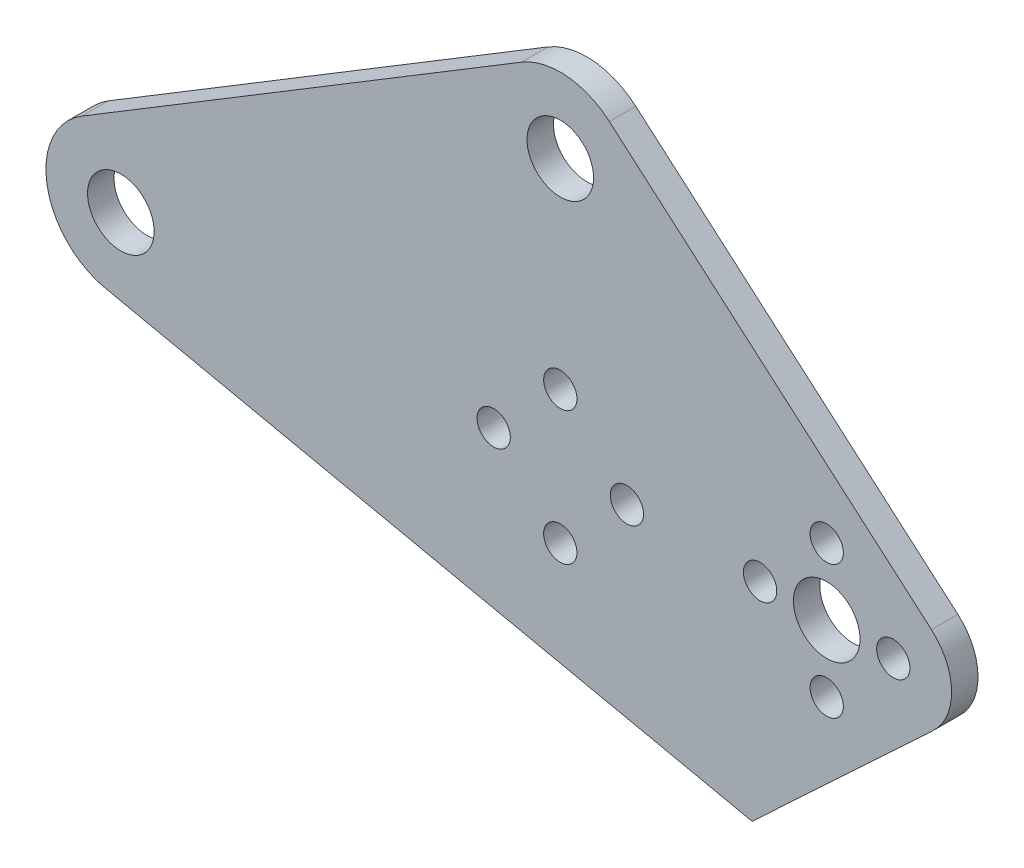
SolidWorks part; units mm, degrees
ref_plane "Front Plane" through (0, 0, 0) normal (0, 0, 1) x (1, 0, 0)
ref_plane "Top Plane" through (0, 0, 0) normal (0, 1, 0) x (1, 0, 0)
ref_plane "Right Plane" through (0, 0, 0) normal (1, 0, 0) x (0, 0, -1)
sketch "Sketch1" plane through (0, 0, 0) normal (0, 0, 1) x (1, 0, 0)
  line L0 (0, 18.4752) -> (52.7846, -12) construction
  line L1 (0, 0) -> (44.7846, 0) construction
  line L2 (-4.6657, 7.6962) -> (48.1189, 39.6962)
  line L3 (58.677, 38.8029) -> (97.3676, 5.2912)
  line L4 (97.5633, -5.1151) -> (75.825, -25.4239)
  line L5 (-1.8827, -8.8009) -> (75.825, -25.4239)
  circle A0 centre (0, 0) radius 4
  circle A1 centre (84.7846, 0) radius 4
  circle A3 centre (60.7846, 0) radius 2
  circle A5 centre (52.7846, -8) radius 2
  circle A6 centre (44.7846, 0) radius 2
  circle A7 centre (52.7846, 8) radius 2
  circle A8 centre (52.7846, 32) radius 4
  circle A9 centre (92.7846, 0) radius 2
  circle A10 centre (84.7846, -8) radius 2
  circle A11 centre (76.7846, 0) radius 2
  circle A12 centre (84.7846, 8) radius 2
  arc A13 (-4.6657, 7.6962) -> (-1.8827, -8.8009) centre (0, 0) ccw
  arc A14 (48.1189, 39.6962) -> (58.677, 38.8029) centre (52.7846, 32) cw
  arc A15 (97.3676, 5.2912) -> (97.5633, -5.1151) centre (92.7846, 0) cw
  point P10 (52.7846, 0)
  point P15 (52.7846, 0)
  point P31 (84.7846, 0)
  point P35 (98.4241, 3.0009)
  point P36 (0, 0)
  point P38 (0, 0)
  point P39 (0, 0)
  point P40 (0, 0)
  point P41 (0, 0)
  dimension "D1" = 8
  dimension "D3" = 4
  dimension "D12" = 5
  dimension "D13" = 5
  dimension "D2" = 8
  dimension "D5" = 32
  dimension "D6" = 32
  dimension "D7" = 16
  dimension "D8" = 30
  dimension "D9" = 2
  dimension "D10" = 8
  dimension "D4" = 4
  dimension "D11" = 4
extrude "Boss-Extrude1" add sketch "Sketch1" along normal blind 3.175
